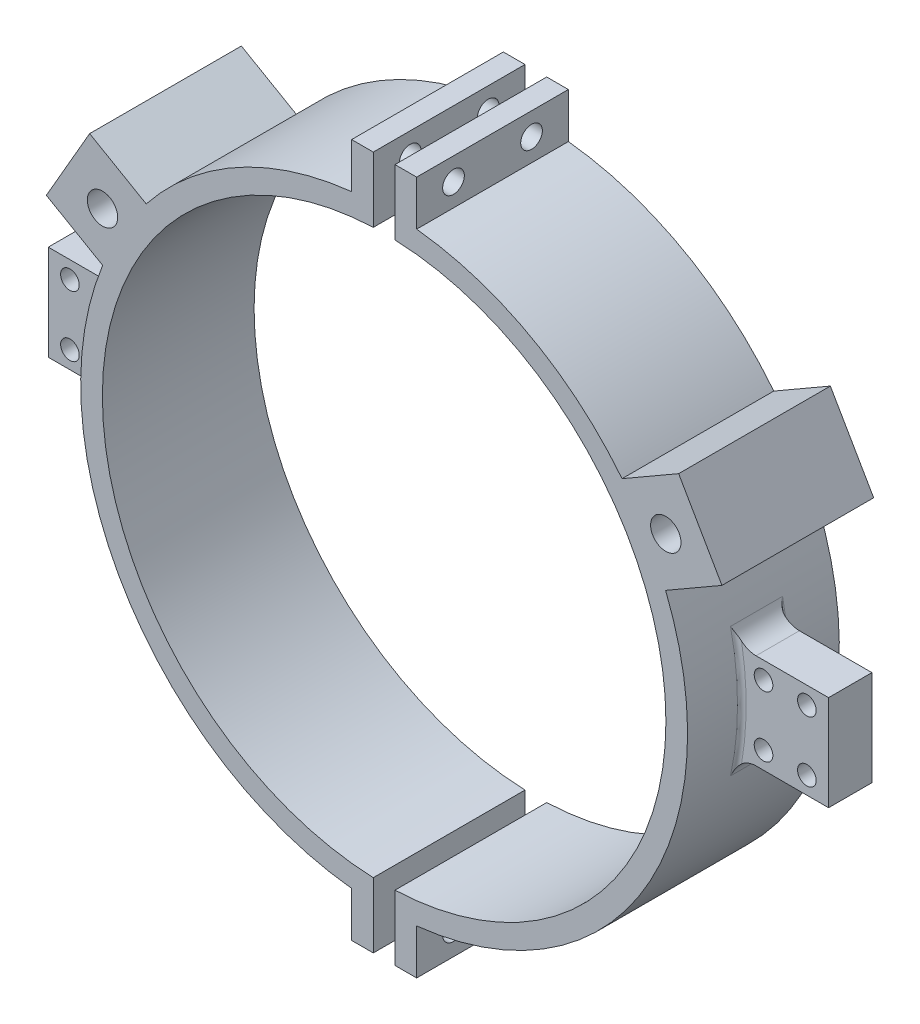
SolidWorks part; units mm, degrees
material "PEI"
ref_plane "前视基准面" through (0, 0, 0) normal (0, 0, 1) x (1, 0, 0)
ref_plane "上视基准面" through (0, 0, 0) normal (0, 1, 0) x (1, 0, 0)
ref_plane "右视基准面" through (0, 0, 0) normal (1, 0, 0) x (0, 0, -1)
other "Configuration Table"
sketch "草图2" plane through (0, 0, 0) normal (0, 0, 1) x (1, 0, 0)
  circle A0 centre (0, 0) radius 65
  circle A1 centre (0, 0) radius 70
  dimension "D1" = 130
  dimension "D2" = 5
extrude "凸台-拉伸1" add sketch "草图2" along normal blind 35
ref_plane "基准面1" through (0, 80, 0) normal (0, 1, 0) x (1, 0, 0)
sketch "草图3" plane through (0, 80, 0) normal (0, 1, 0) x (1, 0, 0)
  line L0 (-70, -35) -> (70, -35) construction
  line L2 (-7.5, 0) -> (-7.5, -35)
  line L3 (-7.5, -35) -> (7.5, -35)
  line L4 (7.5, 0) -> (7.5, -35)
  line L7 (-7.5, 0) -> (7.5, 0)
  point P0 (0, 0)
  dimension "D1" = 15
extrude "凸台-拉伸2" add sketch "草图3" against normal up to next
ref_plane "基准面2" through (0, -80, 0) normal (0, 1, 0) x (1, 0, 0)
sketch "草图4" plane through (0, -80, 0) normal (0, 1, 0) x (1, 0, 0)
  line L0 (-7.5, -35) -> (7.5, -35) construction
  line L1 (7.5, -35) -> (7.5, 0) construction
  line L2 (7.5, 0) -> (-7.5, 0) construction
  line L3 (-7.5, 0) -> (-7.5, -35) construction
  line L4 (-7.5, -35) -> (7.5, -35)
  line L5 (7.5, -35) -> (7.5, 0)
  line L6 (7.5, 0) -> (-7.5, 0)
  line L7 (-7.5, 0) -> (-7.5, -35)
extrude "凸台-拉伸3" add sketch "草图4" along normal up to next
sketch "草图5" plane through (0, 80, 0) normal (0, 1, 0) x (1, 0, 0)
  line L0 (-7.5, -35) -> (7.5, -35) construction
  line L2 (-2.5, 0) -> (-2.5, -35)
  line L3 (-2.5, -35) -> (2.5, -35)
  line L4 (2.5, 0) -> (2.5, -35)
  line L7 (-2.5, 0) -> (2.5, 0)
  point P0 (0, 0)
  dimension "D1" = 5
extrude "切除-拉伸1" cut sketch "草图5" against normal blind 18
sketch "草图6" plane through (0, -80, 0) normal (0, 1, 0) x (1, 0, 0)
  line L0 (-65, -35) -> (65, -35) construction
  line L1 (65, 0) -> (-65, 0) construction
  line L2 (2.5, 0) -> (2.5, -35) construction
  line L3 (-2.5, -35) -> (-2.5, 0) construction
  line L4 (-2.5, -35) -> (2.5, -35)
  line L5 (2.5, 0) -> (-2.5, 0)
  line L6 (2.5, 0) -> (2.5, -35)
  line L7 (-2.5, -35) -> (-2.5, 0)
extrude "切除-拉伸3" cut sketch "草图6" along normal blind 18
sketch "草图7" plane through (-7.5, 0, 0) normal (-1, 0, 0) x (0, 0, 1)
  line L0 (0, -69.5971) -> (35, -80) construction
  line L1 (19.25, -80) -> (-19.25, -80) construction
  line L2 (0, -80) -> (35, -69.5971) construction
  line L3 (17.5, -74.7985) -> (17.5, -70.9157) construction
  circle A1 centre (8.5, -74.4637) radius 2.5
  circle A2 centre (26.5, -74.4637) radius 2.5
  dimension "D1" = 9
extrude "切除-拉伸4" cut sketch "草图7" against normal blind 18
sketch "草图8" plane through (-7.5, 0, 0) normal (-1, 0, 0) x (0, 0, 1)
  line L0 (0, 69.5971) -> (35, 80) construction
  line L1 (19.25, 80) -> (-19.25, 80) construction
  line L2 (35, 69.5971) -> (35, 80) construction
  line L3 (35, 69.5971) -> (0, 80) construction
  line L4 (0, 69.5971) -> (0, 80) construction
  line L5 (17.5, 74.7985) -> (17.5, 84.6515) construction
  circle A1 centre (8.5, 74.7985) radius 2.5
  circle A2 centre (26.5, 74.7985) radius 2.5
  dimension "D1" = 9
extrude "切除-拉伸5" cut sketch "草图8" against normal blind 18
ref_plane "基准面3" through (90, 0, 0) normal (1, 0, 0) x (0, 0, -1)
sketch "草图9" plane through (90, 0, 0) normal (1, 0, 0) x (0, 0, -1)
  line L0 (-34.9606, 80) -> (0, -80) construction
  line L1 (19.25, 80) -> (-19.25, 80) construction
  line L2 (19.25, -80) -> (-19.25, -80) construction
  line L3 (0, -69.5971) -> (0, -80) construction
  line L4 (0, 80) -> (-35, -80) construction
  line L5 (-35, -69.5971) -> (-35, -80) construction
  line L7 (-12.4803, 11) -> (-22.4803, 11)
  line L8 (-12.4803, 11) -> (-12.4803, -11)
  line L9 (-12.4803, -11) -> (-22.4803, -11)
  line L10 (-22.4803, 11) -> (-22.4803, -11)
  line L11 (-12.4803, 11) -> (-22.4803, -11) construction
  line L12 (-12.4803, -11) -> (-22.4803, 11) construction
  point P12 (-17.4803, 0)
  dimension "D1" = 22
  dimension "D2" = 10
extrude "凸台-拉伸4" add sketch "草图9" against normal up to next
ref_plane "基准面4" through (-90, 0, 0) normal (1, 0, 0) x (0, 0, -1)
sketch "草图10" plane through (-90, 0, 0) normal (1, 0, 0) x (0, 0, -1)
  line L0 (-22.4803, -11) -> (-12.4803, -11) construction
  line L1 (-12.4803, -11) -> (-12.4803, 11) construction
  line L2 (-12.4803, 11) -> (-22.4803, 11) construction
  line L3 (-22.4803, 11) -> (-22.4803, -11) construction
  line L4 (-22.4803, -11) -> (-12.4803, -11)
  line L5 (-12.4803, -11) -> (-12.4803, 11)
  line L6 (-12.4803, 11) -> (-22.4803, 11)
  line L7 (-22.4803, 11) -> (-22.4803, -11)
extrude "凸台-拉伸5" add sketch "草图10" along normal up to next
sketch "草图11" plane through (0, 0, 22.4803) normal (0, 0, 1) x (1, 0, 0)
  line L0 (90, -19.25) -> (90, 19.25) construction
  line L1 (69.1303, 11) -> (90, 11) construction
  line L2 (0, 0) -> (50.0992, 0) construction
  line L3 (0, 0) -> (0, 46.0597) construction
  circle A0 centre (85, 7) radius 2.15
  circle A1 centre (85, -7) radius 2.15
  circle A2 centre (-85, -7) radius 2.15
  circle A3 centre (-85, 7) radius 2.15
  circle A4 centre (75, 7) radius 2.15
  circle A5 centre (75, -7) radius 2.15
  circle A6 centre (-75, -7) radius 2.15
  circle A7 centre (-75, 7) radius 2.15
  dimension "D1" = 5
  dimension "D3" = 15
  dimension "D5" = 4.3
  dimension "D6" = 4.3
  dimension "D2" = 4
  dimension "D4" = 4
extrude "切除-拉伸6" cut sketch "草图11" against normal blind 10
sketch "草图12" plane through (0, 0, 0) normal (0, 0, -1) x (-1, 0, 0)
  line L0 (0, 0) -> (0, 54.361) construction
  line L1 (0, 0) -> (-98.4202, 56.7543) construction
  line L2 (-77.9247, 33.6475) -> (-67.9338, 50.9732)
  line L3 (-67.9338, 50.9732) -> (-54.8841, 43.4481)
  line L4 (-77.9247, 33.6475) -> (-64.9304, 26.1543)
  line L5 (77.9247, 33.6475) -> (64.9304, 26.1543)
  line L6 (77.9247, 33.6475) -> (67.9338, 50.9732)
  line L7 (67.9338, 50.9732) -> (54.8841, 43.4481)
  circle A0 centre (-64.9715, 37.466) radius 3.5
  circle A1 centre (64.9715, 37.466) radius 3.5
  arc A2 (-7.5, 69.5971) -> (-7.5, -69.5971) centre (0, 0) ccw construction
  arc A3 (7.5, -69.5971) -> (7.5, 69.5971) centre (0, 0) ccw construction
  arc A4 (64.9304, 26.1543) -> (54.8841, 43.4481) centre (0, 0) ccw
  arc A5 (-54.8841, 43.4481) -> (-64.9304, 26.1543) centre (0, 0) ccw
  dimension "D2" = 7
  dimension "D1" = 60.03
  dimension "D3" = 20
  dimension "D4" = 90
  dimension "D5" = 90
  dimension "D6" = 75
  dimension "D7" = 15
extrude "凸台-拉伸6" add sketch "草图12" against normal up to vertex (35 mm away) up to point (2.5, -64.9519, 35)
fillet "圆角1" radius 5 2 edges at (69.1303, -11, 17.4803) (69.1303, 11, 17.4803)
fillet "圆角2" radius 5 2 edges at (-69.1303, -11, 17.4803) (-69.1303, 11, 17.4803)
fillet "圆角3" radius 1 1 edges at (-70, 0, 12.4803)
fillet "圆角4" radius 1 1 edges at (-70, 0, 22.4803)
fillet "圆角5" radius 1 2 edges at (70, 0, 12.4803) (70, 0, 22.4803)
